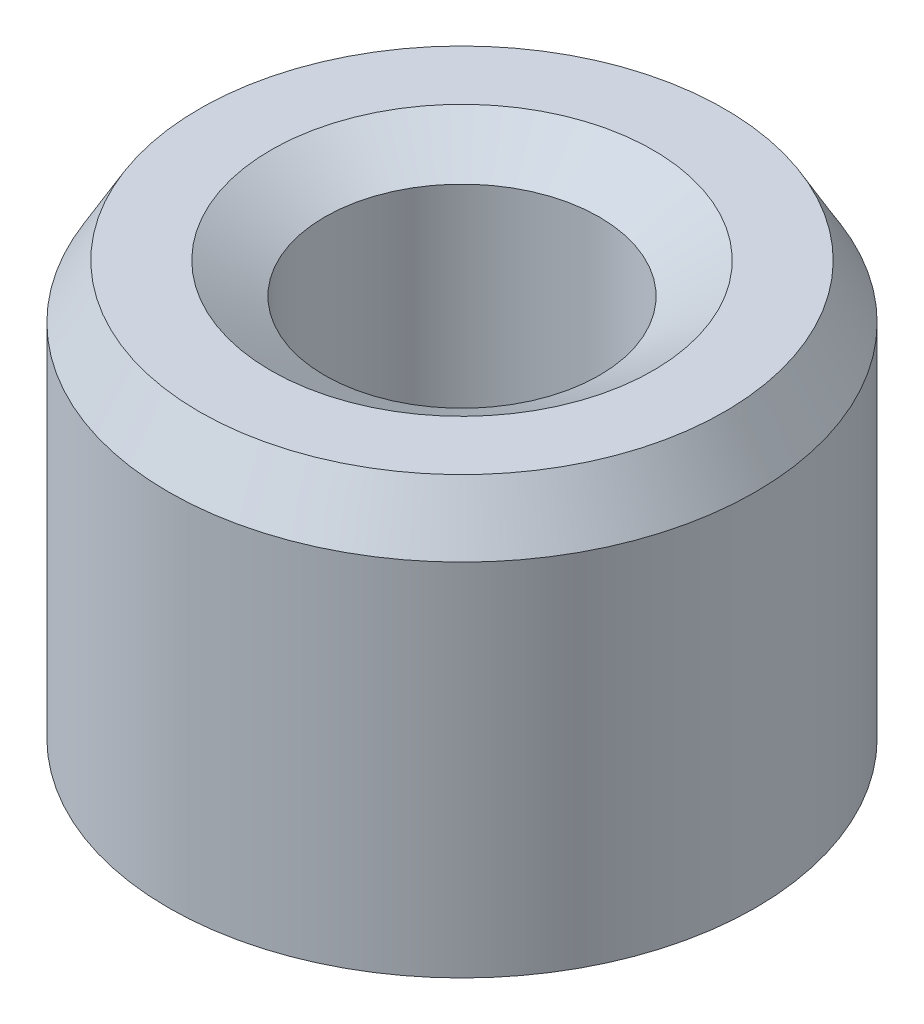
SolidWorks part; units mm, degrees
ref_plane "Front Plane" through (0, 0, 0) normal (0, 0, 1) x (1, 0, 0)
ref_plane "Top Plane" through (0, 0, 0) normal (0, 1, 0) x (1, 0, 0)
ref_plane "Right Plane" through (0, 0, 0) normal (1, 0, 0) x (0, 0, -1)
sketch "Sketch1" plane through (0, 0, 0) normal (0, 1, 0) x (1, 0, 0)
  circle A0 centre (0, 0) radius 5
  dimension "SLEEVE_OD" = 10
extrude "Boss-Extrude1" add sketch "Sketch1" along normal blind 7.5798
sketch "Sketch2" plane through (0, 0, 0) normal (0, 1, 0) x (1, 0, 0)
  circle A0 centre (0, 0) radius 2.3381
  dimension "BORE_D" = 4.6761
extrude "Cut-Extrude1" cut sketch "Sketch2" along normal through all
chamfer "Chamfer1" distance 0.9167 angle 30 4 edges at (0, 7.5798, 2.3381) (0, 0, 2.3381) (0, 0, 5) (0, 7.5798, 5) first distance on face at (0, 7.5798, 2.3381) first distance on face at (0, 0, 2.3381) first distance on face at (0, 7.5798, 5)
